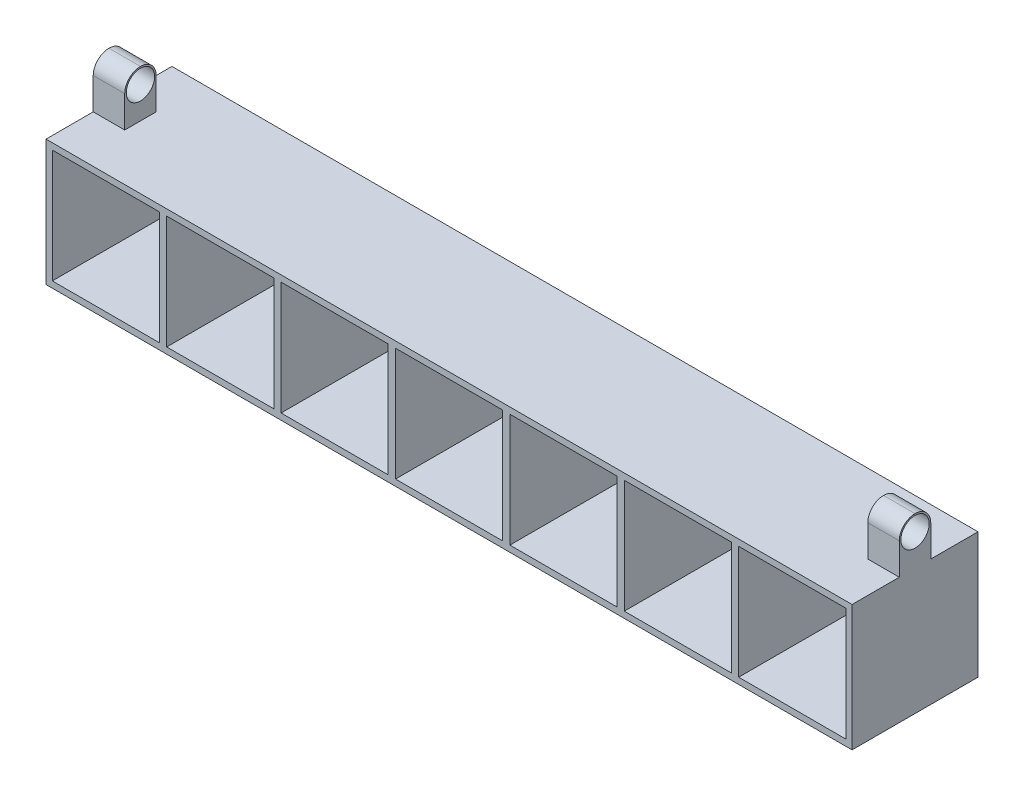
SolidWorks part; units mm, degrees
ref_plane "Front Plane" through (0, 0, 0) normal (0, 0, 1) x (1, 0, 0)
ref_plane "Top Plane" through (0, 0, 0) normal (0, 1, 0) x (1, 0, 0)
ref_plane "Right Plane" through (0, 0, 0) normal (1, 0, 0) x (0, 0, -1)
sketch "Sketch1" plane through (0, 0, 0) normal (0, 0, 1) x (1, 0, 0)
  line L1 (0, 0) -> (2560, 0)
  line L2 (0, 0) -> (0, -400)
  line L3 (0, -400) -> (2560, -400)
  line L4 (2560, 0) -> (2560, -400)
  dimension "D1" = 400
  dimension "D2" = 2560
extrude "Boss-Extrude1" add sketch "Sketch1" along normal blind 400
sketch "Sketch2" plane through (0, 0, 400) normal (0, 0, 1) x (1, 0, 0)
  line L0 (0, 0) -> (0, -400) construction
  line L1 (20, -20) -> (360, -20)
  line L2 (20, -20) -> (20, -380)
  line L3 (20, -380) -> (360, -380)
  line L4 (360, -20) -> (360, -380)
  line L5 (2560, 0) -> (0, 0) construction
  line L6 (0, -400) -> (2560, -400) construction
  line L7 (383.3333, -20) -> (383.3333, -380)
  line L8 (383.3333, -20) -> (723.3333, -20)
  line L9 (723.3333, -20) -> (723.3333, -380)
  line L10 (383.3333, -380) -> (723.3333, -380)
  line L11 (746.6667, -20) -> (746.6667, -380)
  line L12 (746.6667, -20) -> (1086.6667, -20)
  line L13 (1086.6667, -20) -> (1086.6667, -380)
  line L14 (746.6667, -380) -> (1086.6667, -380)
  line L15 (1110, -20) -> (1110, -380)
  line L16 (1110, -20) -> (1450, -20)
  line L17 (1450, -20) -> (1450, -380)
  line L18 (1110, -380) -> (1450, -380)
  line L19 (1473.3333, -20) -> (1473.3333, -380)
  line L20 (1473.3333, -20) -> (1813.3333, -20)
  line L21 (1813.3333, -20) -> (1813.3333, -380)
  line L22 (1473.3333, -380) -> (1813.3333, -380)
  line L23 (1836.6667, -20) -> (1836.6667, -380)
  line L24 (1836.6667, -20) -> (2176.6667, -20)
  line L25 (2176.6667, -20) -> (2176.6667, -380)
  line L26 (1836.6667, -380) -> (2176.6667, -380)
  line L27 (2200, -20) -> (2200, -380)
  line L28 (2200, -20) -> (2540, -20)
  line L29 (2540, -20) -> (2540, -380)
  line L30 (2200, -380) -> (2540, -380)
  line L31 (2560, -400) -> (2560, 0) construction
  point P36 (2560, -200)
  dimension "D1" = 20
  dimension "D2" = 20
  dimension "D3" = 20
  dimension "D4" = 340
  dimension "D6" = 20
  dimension "D5" = 7
extrude "Cut-Extrude1" cut sketch "Sketch2" against normal blind 380
sketch "Sketch3" plane through (0, 0, 0) normal (0, 1, 0) x (1, 0, 0)
  line L0 (0, -400) -> (0, 0) construction
  line L1 (0, -150) -> (100, -150)
  line L2 (0, -150) -> (0, -250)
  line L3 (0, -250) -> (100, -250)
  line L4 (100, -150) -> (100, -250)
  dimension "D1" = 100
  dimension "D2" = 100
  dimension "D3" = 150
extrude "Boss-Extrude2" add sketch "Sketch3" along normal blind 150
fillet "Fillet1" radius 50 2 edges at (50, 150, 150) (50, 150, 250)
sketch "Sketch4" plane through (0, 0, 0) normal (0, 1, 0) x (1, 0, 0)
  line L0 (2560, -400) -> (2560, 0) construction
  line L1 (2560, -150) -> (2460, -150)
  line L2 (2560, -150) -> (2560, -250)
  line L3 (2560, -250) -> (2460, -250)
  line L4 (2460, -150) -> (2460, -250)
  line L6 (2560, 0) -> (0, 0) construction
  dimension "D1" = 100
  dimension "D2" = 100
  dimension "D3" = 150
extrude "Boss-Extrude3" add sketch "Sketch4" along normal blind 150
fillet "Fillet2" radius 50 2 edges at (2510, 150, 150) (2510, 150, 250)
sketch "Sketch5" plane through (2560, 0, 0) normal (1, 0, 0) x (0, 0, -1)
  line L0 (-150, 100) -> (-150, 0) construction
  circle A0 centre (-200, 100) radius 45
  dimension "D1" = 90
  dimension "D2" = 50
  dimension "D3" = 50
extrude "Cut-Extrude2" cut sketch "Sketch5" against normal through all both and the other way through all
